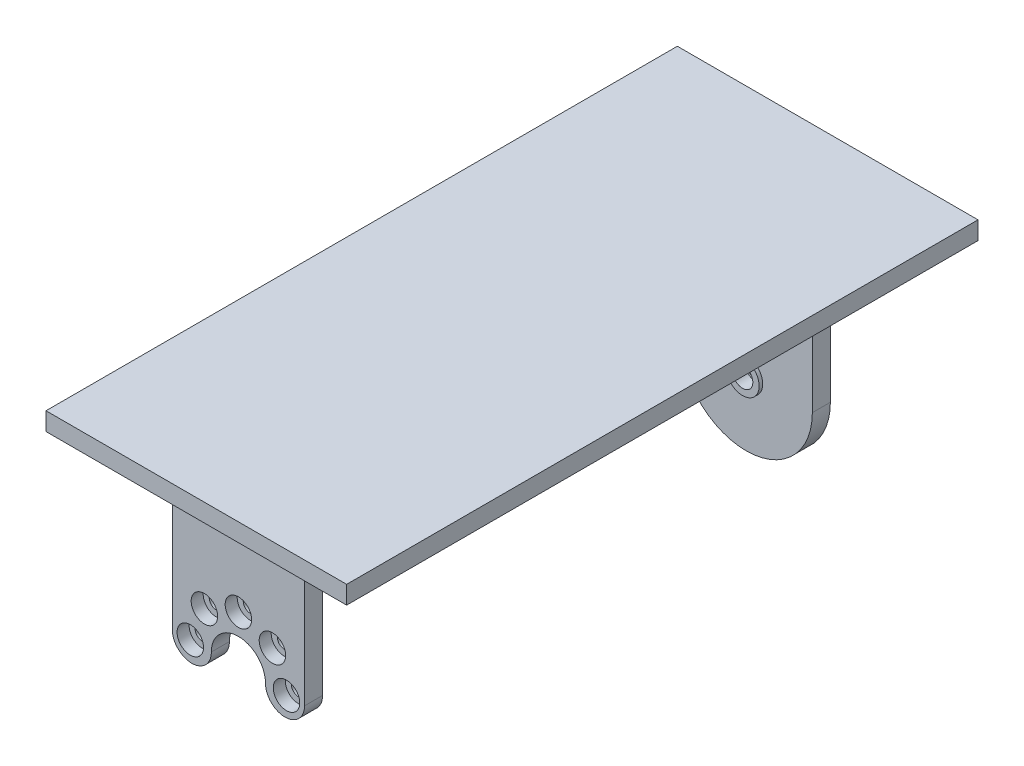
SolidWorks part; units mm, degrees
ref_plane "Plano frontal" through (0, 0, 0) normal (0, 0, 1) x (1, 0, 0)
ref_plane "Plano superior" through (0, 0, 0) normal (0, 1, 0) x (1, 0, 0)
ref_plane "Plano direito" through (0, 0, 0) normal (1, 0, 0) x (0, 0, -1)
sketch "Esboço1" plane through (0, 0, 0) normal (0, 0, 1) x (1, 0, 0)
  line L0 (11, 0) -> (11, 25)
  line L1 (11, 25) -> (-11, 25)
  line L2 (-11, 25) -> (-11, 0)
  arc A3 (11, 0) -> (4.5, 0) centre (7.75, 0) cw
  arc A8 (4.5, 0) -> (-4.5, 0) centre (0, 0) ccw
  arc A10 (-4.5, 0) -> (-11, 0) centre (-7.75, 0) cw
  dimension "D1" = 25
extrude "Ressalto-extrusão1" add sketch "Esboço1" along normal blind 3
sketch "Esboço2" plane through (0, 25, 0) normal (0, 1, 0) x (1, 0, 0)
  line L1 (-25, -10) -> (25, -10)
  line L2 (-25, -10) -> (-25, 95)
  line L3 (-25, 95) -> (25, 95)
  line L4 (25, -10) -> (25, 95)
  line L5 (11, -3) -> (-11, -3) construction
  point P7 (0, -3)
  point P8 (0, -10)
  dimension "D1" = 105
  dimension "D2" = 50
  dimension "D3" = 7
extrude "Ressalto-extrusão2" add sketch "Esboço2" along normal blind 3
ref_plane "Plano1" through (0, 0, -81.45) normal (0, 0, -1) x (-1, 0, 0)
sketch "Esboço3" plane through (0, 0, -81.45) normal (0, 0, -1) x (-1, 0, 0)
  line L1 (-11, 0) -> (-11, 25)
  line L2 (-11, 25) -> (11, 25)
  line L3 (11, 25) -> (11, 0)
  arc A0 (-11, 0) -> (11, 0) centre (0, 0) ccw
  dimension "D1" = 22
extrude "Ressalto-extrusão3" add sketch "Esboço3" along normal blind 3
hole_wizard "Rebaixo para SHCS M21" positions "Esboço4" profile "Esboço5" counterbore size "M2" standard "Ansi Metric" end condition up to next
sketch "Esboço4" plane through (0, 0, 3) normal (0, 0, 1) x (1, 0, 0)
  arc A0 (8.8, 0) -> (7.2, 0) centre (8, 0) ccw construction
  point P0 (8, 0)
sketch "Esboço5" plane through (8, 0, 3) normal (1, 0, 0) x (0, -1, 0)
  line L0 (0, 0) -> (0, 3)
  line L1 (0, 3) -> (1.2, 3)
  line L3 (1.2, 3) -> (1.2, 2)
  line L4 (1.2, 2) -> (2.2, 2)
  line L5 (2.2, 2) -> (2.2, 0)
  line L7 (2.2, 0) -> (0, 0)
  line L11 (0, -6.35) -> (0, 107.95) construction
  dimension "Thru Hole Dia." = 2.4
  dimension "Thru Hole Depth" = 3
  dimension "C'Bore Dia." = 4.4
  dimension "C'Bore Depth" = 2
pattern_circular "PadrãoCircular1" count 5 over 180 about axis through (0, 0, 3) along (0, 0, -1) of "Rebaixo para SHCS M21" reverse direction yes
sketch "Esboço6" plane through (0, 0, 0) normal (1, 0, 0) x (0, 0, -1)
  line L0 (-10, 25) -> (-3, 25) construction
  line L3 (-3, 25) -> (-3, 18) construction
  line L4 (-3, 0) -> (-3, 25) construction
  line L5 (-3, 18) -> (-10, 25)
rib "Nervura1" sketch "Esboço6" sketch "Esboço6" thickness 15 extrusion direction parallel to sketch draft on no parameters "D1"=15
sketch "Esboço7" plane through (0, 0, 3) normal (0, 0, 1) x (1, 0, 0)
  line L0 (-7.5, 25) -> (7.5, 25) construction
  line L1 (-5, 25) -> (5, 25)
  line L2 (-5, 25) -> (-5, 18)
  line L3 (-5, 18) -> (5, 18)
  line L4 (5, 25) -> (5, 18)
  line L5 (7.5, 18) -> (-7.5, 18) construction
  point P8 (0, 18)
  point P9 (0, 18)
  dimension "D1" = 10
extrude "Corte-extrusão1" cut sketch "Esboço7" along normal up to surface (7 mm away) up to face at (0, 21.5, 6.5)
sketch "Esboço8" plane through (0, 0, 0) normal (1, 0, 0) x (0, 0, -1)
  line L0 (0, 18) -> (7, 25)
  line L1 (0, 0) -> (0, 25) construction
  line L2 (-10, 25) -> (95, 25) construction
  line L5 (-10, 25) -> (-3, 18) construction
rib "Nervura7" sketch "Esboço8" sketch "Esboço8" thickness 15 extrusion direction parallel to sketch draft on no parameters "D1"=15
sketch "Esboço9" plane through (0, 0, 0) normal (0, 0, -1) x (-1, 0, 0)
  line L0 (-7.5, 18) -> (7.5, 18) construction
  line L1 (-5, 18) -> (5, 18)
  line L2 (-5, 18) -> (-5, 25)
  line L3 (-5, 25) -> (5, 25)
  line L4 (5, 18) -> (5, 25)
  line L5 (-11, 25) -> (-7.5, 25) construction
  point P8 (0, 18)
  point P9 (0, 18)
  dimension "D1" = 10
extrude "Corte-extrusão2" cut sketch "Esboço9" along normal up to surface up to face at (0, 21.5, -3.5)
pattern_linear "Padrão linear1" count 2 spacing 84.45 along (0, 0, -1) of "Nervura1", "Nervura7", "Corte-extrusão2", "Corte-extrusão1"
sketch "Esboço10" plane through (0, 0, -81.45) normal (0, 0, 1) x (1, 0, 0)
  circle A0 centre (0, 0) radius 2.75
  circle A2 centre (0, 0) radius 3.25 construction
  dimension "D1" = 0.5
extrude "Ressalto-extrusão4" add sketch "Esboço10" along normal offset from surface (0.6 mm away) 0.25 contours A0
hole_wizard "Rebaixo para parafuso com cabeça panela de M31" positions "Esboço11" profile "Esboço12" counterbore size "M3" standard "DIN" end condition up to next
sketch "Esboço11" plane through (0, 0, -84.45) normal (0, 0, -1) x (-1, 0, 0)
  circle A0 centre (0, 0) radius 3.25 construction
  point P0 (0, 0)
  point P3 (0, 0)
sketch "Esboço12" plane through (0, 0, -84.45) normal (1, 0, 0) x (0, 1, 0)
  line L0 (0, 0) -> (0, 3.6)
  line L1 (0, 3.6) -> (1.7, 3.6)
  line L3 (1.7, 3.6) -> (1.7, 1.5)
  line L4 (1.7, 1.5) -> (3.5, 1.5)
  line L5 (3.5, 1.5) -> (3.5, 0)
  line L7 (3.5, 0) -> (0, 0)
  line L11 (0, -6.35) -> (0, 107.95) construction
  dimension "Thru Hole Dia." = 3.4
  dimension "Thru Hole Depth" = 3.6
  dimension "C'Bore Dia." = 7
  dimension "C'Bore Depth" = 1.5
